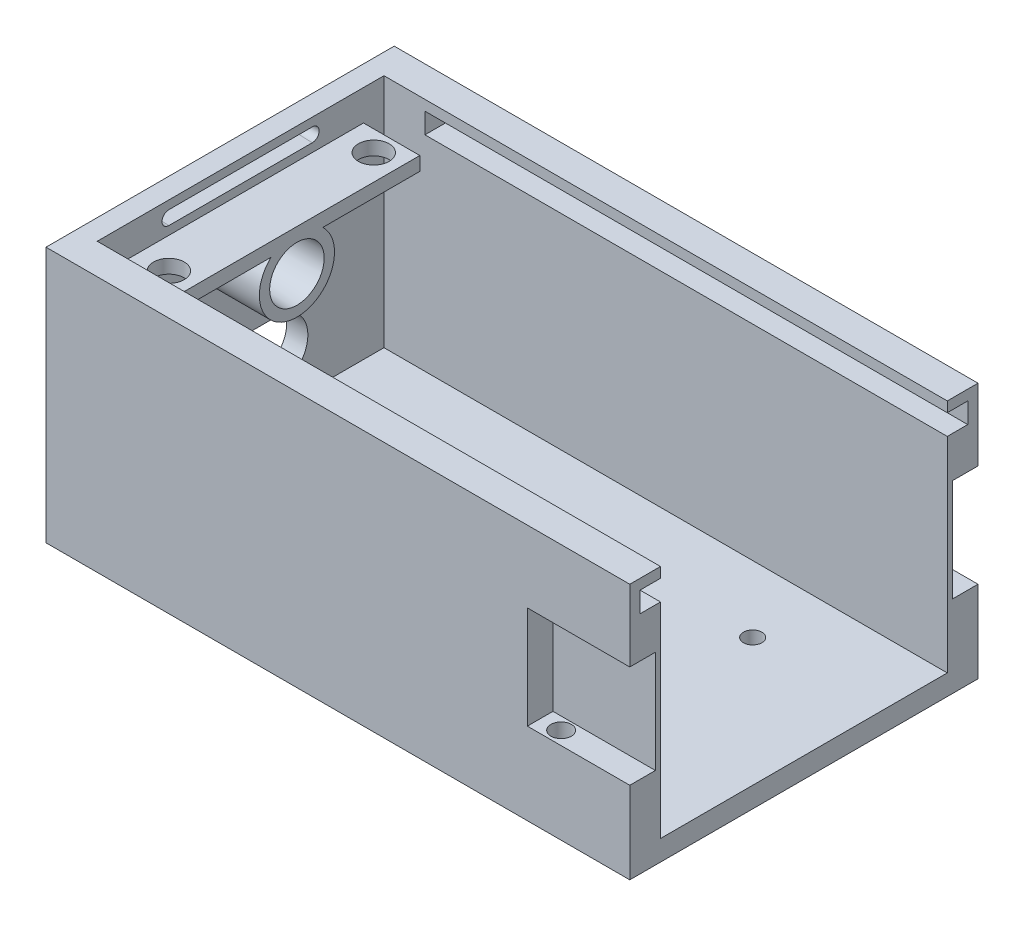
SolidWorks part; units mm, degrees
ref_plane "Front Plane" through (0, 0, 0) normal (0, 0, 1) x (1, 0, 0)
ref_plane "Top Plane" through (0, 0, 0) normal (0, 1, 0) x (1, 0, 0)
ref_plane "Right Plane" through (0, 0, 0) normal (1, 0, 0) x (0, 0, -1)
sketch "Sketch1" plane through (0, 0, 0) normal (0, 1, 0) x (1, 0, 0)
  line L1 (0, 0) -> (59, 0)
  line L2 (0, 0) -> (0, 34)
  line L3 (0, 34) -> (59, 34)
  line L4 (59, 0) -> (59, 34)
  line L5 (0, 0) -> (59, 34) construction
  line L6 (0, 34) -> (59, 0) construction
  line L7 (2, 3) -> (57, 3)
  line L8 (2, 3) -> (2, 31)
  line L9 (2, 31) -> (57, 31)
  line L10 (57, 3) -> (57, 31)
  line L11 (2, 3) -> (57, 31) construction
  line L12 (2, 31) -> (57, 3) construction
  point P4 (29.5, 17)
  point P6 (29.5, 17)
  dimension "D1" = 59
  dimension "D2" = 34
  dimension "D3" = 3
  dimension "D4" = 2
extrude "Boss-Extrude1" add sketch "Sketch1" along normal blind 25
extrude "Boss-Extrude2" add sketch "Sketch1<2>" along normal blind 2 contours L10 L9 L8 L7
sketch "Sketch1<2>" plane through (0, 0, 0) normal (0, 1, 0) x (1, 0, 0) same geometry as "Sketch1"
sketch "Sketch2" plane through (0, 25, 0) normal (0, 1, 0) x (1, 0, 0)
  line L0 (59, 34) -> (0, 34) construction
  line L1 (59, 0) -> (57, 0)
  line L2 (59, 0) -> (59, 34)
  line L3 (59, 34) -> (57, 34)
  line L4 (57, 0) -> (57, 34)
  line L5 (59, 0) -> (57, 34) construction
  line L6 (59, 34) -> (57, 0) construction
  point P4 (58, 17)
  dimension "D1" = 2
extrude "Cut-Extrude1" cut sketch "Sketch2" against normal blind 25
sketch "Sketch3" plane through (0, 2, 0) normal (0, 1, 0) x (1, 0, 0)
  line L0 (2, 31) -> (57, 31) construction
  line L2 (2, 3) -> (2, 31) construction
  line L3 (2, 31) -> (57, 31) construction
  circle A0 centre (4, 9.5) radius 0.9
  circle A1 centre (4, 24.5) radius 0.9
  circle A2 centre (44.5, 9.5) radius 0.9
  circle A3 centre (44.5, 24.5) radius 0.9
  dimension "D1" = 1.8
  dimension "D2" = 1.8
  dimension "D3" = 1.8
  dimension "D4" = 1.8
  dimension "D5" = 40.5
  dimension "D6" = 40.5
  dimension "D7" = 15
  dimension "D8" = 15
  dimension "D9" = 2
  dimension "D10" = 6.5
  dimension "D11" = 6.5
extrude "Cut-Extrude2" cut sketch "Sketch3" against normal blind 25 contours A2 | A3 | A1 | A0
sketch "Sketch4" plane through (0, 0, 0) normal (-1, 0, 0) x (0, 0, 1)
  line L0 (-20.5, 6.8) -> (-13.5, 6.8) construction
  line L1 (-20.5, 9.8) -> (-13.5, 9.8)
  line L2 (-20.5, 3.8) -> (-13.5, 3.8)
  line L3 (-3, 2) -> (-31, 2) construction
  line L4 (0, 25) -> (0, 0) construction
  line L5 (-24, 23.5) -> (-10, 23.5) construction
  line L6 (-24, 24.1) -> (-10, 24.1)
  line L7 (-24, 22.9) -> (-10, 22.9)
  line L8 (-34, 25) -> (0, 25) construction
  arc A0 (-20.5, 9.8) -> (-20.5, 3.8) centre (-20.5, 6.8) ccw
  arc A1 (-13.5, 3.8) -> (-13.5, 9.8) centre (-13.5, 6.8) ccw
  arc A2 (-24, 24.1) -> (-24, 22.9) centre (-24, 23.5) ccw
  arc A3 (-10, 22.9) -> (-10, 24.1) centre (-10, 23.5) ccw
  circle A4 centre (-17, 18) radius 2.4
  point P2 (-17, 6.8)
  point P13 (-17, 23.5)
  dimension "D9" = 4.8
  dimension "D11" = 17
  dimension "D1" = 7
  dimension "D2" = 6
  dimension "D3" = 1.8
  dimension "D4" = 17
  dimension "D5" = 1.2
  dimension "D6" = 14
  dimension "D7" = 0
  dimension "D8" = 1.5
  dimension "D10" = 7
extrude "Cut-Extrude3" cut sketch "Sketch4" against normal blind 25 contours L2 A1 L1 A0 | L6 A3 L7 A2 region at (0, 6.8, -17)
sketch "Sketch5" plane through (57, 0, 0) normal (1, 0, 0) x (0, 0, -1)
  line L0 (3, 25) -> (3, 2) construction
  line L1 (3, 24) -> (1, 24)
  line L2 (3, 24) -> (3, 22)
  line L3 (3, 22) -> (1, 22)
  line L4 (1, 24) -> (1, 22)
  line L5 (3, 24) -> (1, 22) construction
  line L6 (3, 22) -> (1, 24) construction
  line L7 (17, 0) -> (17, 18.6218) construction
  line L8 (3, 0) -> (31, 0) construction
  line L9 (3, 25) -> (0, 25) construction
  line L10 (31, 22) -> (33, 22)
  line L11 (33, 24) -> (33, 22)
  line L12 (31, 24) -> (33, 24)
  line L13 (31, 24) -> (31, 22)
  point P4 (2, 23)
  dimension "D1" = 2
  dimension "D2" = 2
  dimension "D3" = 1
extrude "Cut-Extrude4" cut sketch "Sketch5" against normal blind 51
sketch "Sketch6" plane through (2, 0, 0) normal (1, 0, 0) x (0, 0, -1)
  line L0 (31, 25) -> (3, 25) construction
  line L1 (31, 25) -> (31, 2) construction
  circle A0 centre (17, 18) radius 3.6688
  dimension "D1" = 7
  dimension "D2" = 14
extrude "Boss-Extrude3" add sketch "Sketch6" along normal blind 5.5
extrude "Cut-Extrude5" cut sketch "Sketch4<3>" against normal blind 8 draft 2 draft outward yes
sketch "Sketch4<3>" plane through (0, 0, 0) normal (-1, 0, 0) x (0, 0, 1) same geometry as "Sketch4"
sketch "Sketch7" plane through (2, 0, 0) normal (1, 0, 0) x (0, 0, -1)
  line L0 (31, 25) -> (3, 25) construction
  line L1 (5, 22) -> (29, 22)
  line L2 (5, 22) -> (5, 20.6584)
  line L3 (5, 20.6584) -> (29, 20.6584)
  line L4 (29, 22) -> (29, 20.6584)
  line L5 (5, 22) -> (29, 20.6584) construction
  line L6 (5, 20.6584) -> (29, 22) construction
  point P4 (17, 21.3292)
  dimension "D1" = 24
  dimension "D2" = 0
  dimension "D3" = 3
extrude "Boss-Extrude4" add sketch "Sketch7" along normal blind 5.5
sketch "Sketch8" plane through (0, 22, 0) normal (0, 1, 0) x (1, 0, 0)
  line L0 (2, 29) -> (2, 5) construction
  line L1 (2, 29) -> (2, 5) construction
  circle A0 centre (5, 7) radius 1.5
  circle A1 centre (5, 27) radius 1.5
  dimension "D1" = 3
  dimension "D2" = 3
  dimension "D3" = 10
  dimension "D4" = 10
  dimension "D5" = 3
  dimension "D6" = 3
extrude "Cut-Extrude6" cut sketch "Sketch8" against normal blind 5.5 contours A1 | A0 region at (5, 22, -27)
sketch "Sketch9" plane through (0, 0, -34) normal (0, 0, -1) x (-1, 0, 0)
  line L0 (-57, 0) -> (-57, 25) construction
  line L1 (-57, 18) -> (-47, 18)
  line L2 (-57, 18) -> (-57, 8)
  line L3 (-57, 8) -> (-47, 8)
  line L4 (-47, 18) -> (-47, 8)
  line L5 (-57, 18) -> (-47, 8) construction
  line L6 (-57, 8) -> (-47, 18) construction
  line L7 (0, 0) -> (-59, 0) construction
  point P4 (-52, 13)
  dimension "D1" = 8
  dimension "D2" = 10
  dimension "D3" = 10
extrude "Cut-Extrude7" cut sketch "Sketch9" against normal blind 2.5
sketch "Sketch10" plane through (0, 0, 0) normal (0, 0, 1) x (1, 0, 0)
  line L0 (57, 0) -> (57, 25) construction
  line L1 (57, 18) -> (47, 18)
  line L2 (57, 18) -> (57, 8)
  line L3 (57, 8) -> (47, 8)
  line L4 (47, 18) -> (47, 8)
  line L5 (57, 18) -> (47, 8) construction
  line L6 (57, 8) -> (47, 18) construction
  line L7 (0, 0) -> (59, 0) construction
  point P4 (52, 13)
  dimension "D1" = 10
  dimension "D2" = 10
  dimension "D3" = 8
extrude "Cut-Extrude8" cut sketch "Sketch10" against normal blind 2.5
sketch "Sketch11" plane through (0, 18, 0) normal (0, -1, 0) x (-1, 0, 0)
  line L0 (-57, 2.5) -> (-47, 2.5) construction
  line L1 (-47, 2.5) -> (-47, 0) construction
  circle A0 centre (-49, 1.3) radius 1
  dimension "D1" = 2
  dimension "D2" = 1.2
  dimension "D3" = 2
extrude "Cut-Extrude9" cut sketch "Sketch11" against normal blind 2.5 and the other way blind 12.5
sketch "Sketch12" plane through (0, 18, 0) normal (0, -1, 0) x (-1, 0, 0)
  line L0 (-47, 31.5) -> (-47, 34) construction
  line L1 (-47, 31.5) -> (-57, 31.5) construction
  circle A0 centre (-48.8, 32.7) radius 1
  dimension "D2" = 2
  dimension "D1" = 1.8
  dimension "D3" = 1.2
extrude "Cut-Extrude10" cut sketch "Sketch12" against normal blind 2.5 and the other way blind 12.5
